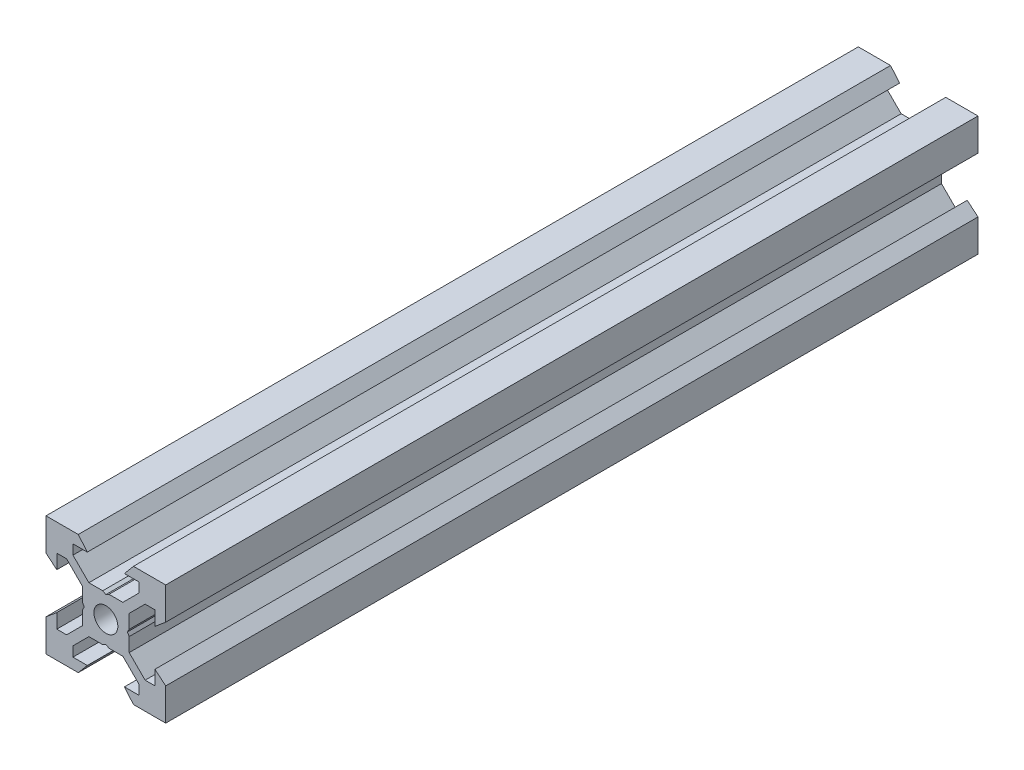
SolidWorks part; units mm, degrees
ref_plane "Front Plane" through (0, 0, 0) normal (0, 0, 1) x (1, 0, 0)
ref_plane "Top Plane" through (0, 0, 0) normal (0, 1, 0) x (1, 0, 0)
ref_plane "Right Plane" through (0, 0, 0) normal (1, 0, 0) x (0, 0, -1)
sketch "Sketch1" plane through (0, 0, 0) normal (0, 0, 1) x (1, 0, 0)
  line L0 (10, 10) -> (4.6104, 10) construction
  line L1 (10, 10) -> (10, 4.6104) construction
  line L2 (10, -10) -> (10, -4.6104) construction
  line L3 (10, -10) -> (4.6104, -10) construction
  line L4 (10, 10) -> (10, 4.6104)
  line L5 (6.5607, 5.5) -> (8.2, 5.5)
  line L6 (5.5, 8.2) -> (5.5, 6.5607)
  line L7 (10, 10) -> (4.6104, 10)
  line L8 (10, 10) -> (10, 4.6104)
  line L9 (6.5607, 5.5) -> (3.9, 2.8393)
  line L10 (5.5, 6.5607) -> (2.8393, 3.9)
  line L11 (10, 4.6104) -> (8.2, 3.1)
  line L12 (4.6104, 10) -> (3.1, 8.2)
  line L13 (8.2, 3.1) -> (8.2, 5.5)
  line L14 (3.1, 8.2) -> (5.5, 8.2)
  line L15 (-6.5607, 5.5) -> (-8.2, 5.5)
  line L16 (6.5607, -5.5) -> (8.2, -5.5)
  line L17 (3.1, -8.2) -> (5.5, -8.2)
  line L18 (8.2, -3.1) -> (8.2, -5.5)
  line L19 (4.6104, -10) -> (3.1, -8.2)
  line L20 (10, -4.6104) -> (8.2, -3.1)
  line L21 (0.5196, -3.9) -> (0, -3.6)
  line L22 (0.5196, 3.9) -> (0, 3.6)
  line L23 (3.6, 0) -> (3.9, -0.5196)
  line L24 (3.9, 0.5196) -> (3.6, 0)
  line L25 (3.9, 0.5196) -> (3.9, 2.8393)
  line L26 (2.8393, 3.9) -> (0.5196, 3.9)
  line L27 (3.9, -2.8393) -> (3.9, -0.5196)
  line L28 (2.8393, -3.9) -> (0.5196, -3.9)
  line L29 (5.5, -6.5607) -> (2.8393, -3.9)
  line L30 (6.5607, -5.5) -> (3.9, -2.8393)
  line L31 (10, -10) -> (10, -4.6104)
  line L32 (10, -10) -> (4.6104, -10)
  line L33 (5.5, -8.2) -> (5.5, -6.5607)
  line L34 (-6.5607, -5.5) -> (-8.2, -5.5)
  line L35 (10, -10) -> (10, -4.6104)
  line L36 (0, 0) -> (0, 8.2) construction
  line L37 (-10, -10) -> (-4.6104, -10) construction
  line L38 (-10, -10) -> (-10, -4.6104) construction
  line L39 (-10, 10) -> (-10, 4.6104) construction
  line L40 (-10, 10) -> (-4.6104, 10) construction
  line L41 (-10, -10) -> (-10, -4.6104)
  line L43 (-5.5, -8.2) -> (-5.5, -6.5607)
  line L44 (-10, -10) -> (-4.6104, -10)
  line L45 (-10, -10) -> (-10, -4.6104)
  line L46 (-6.5607, -5.5) -> (-3.9, -2.8393)
  line L47 (-5.5, -6.5607) -> (-2.8393, -3.9)
  line L48 (-2.8393, -3.9) -> (-0.5196, -3.9)
  line L49 (-3.9, -2.8393) -> (-3.9, -0.5196)
  line L50 (-2.8393, 3.9) -> (-0.5196, 3.9)
  line L51 (-3.9, 0.5196) -> (-3.9, 2.8393)
  line L52 (-3.9, 0.5196) -> (-3.6, 0)
  line L53 (-3.6, 0) -> (-3.9, -0.5196)
  line L54 (-0.5196, 3.9) -> (0, 3.6)
  line L55 (-0.5196, -3.9) -> (0, -3.6)
  line L56 (-10, -4.6104) -> (-8.2, -3.1)
  line L57 (-4.6104, -10) -> (-3.1, -8.2)
  line L58 (-8.2, -3.1) -> (-8.2, -5.5)
  line L59 (-3.1, -8.2) -> (-5.5, -8.2)
  line L60 (-10, -10) -> (10, -10) construction
  line L61 (-10, -10) -> (-10, 10) construction
  line L62 (-3.1, 8.2) -> (-5.5, 8.2)
  line L63 (-8.2, 3.1) -> (-8.2, 5.5)
  line L64 (-4.6104, 10) -> (-3.1, 8.2)
  line L65 (-10, 4.6104) -> (-8.2, 3.1)
  line L66 (-5.5, 6.5607) -> (-2.8393, 3.9)
  line L67 (-6.5607, 5.5) -> (-3.9, 2.8393)
  line L68 (-10, 10) -> (-10, 4.6104)
  line L69 (-10, 10) -> (-4.6104, 10)
  line L70 (-5.5, 8.2) -> (-5.5, 6.5607)
  line L71 (-10, 10) -> (10, 10) construction
  line L72 (-10, 10) -> (-10, 4.6104)
  line L73 (10, -10) -> (10, 10) construction
  line L74 (-10, -10) -> (10, 10) construction
  line L75 (-10, 10) -> (10, -10) construction
  circle A0 centre (0, 0) radius 2
  dimension "D7" = 4
  dimension "D1" = 20
  dimension "D2" = 5.3896
  dimension "D3" = 4.5
  dimension "D4" = 50
  dimension "D5" = 1.8
  dimension "D6" = 1.5104
  dimension "D8" = 5.5
  dimension "D9" = 120
  dimension "D10" = 0.3
  dimension "D11" = 2.3197
  dimension "D12" = 7.8
  dimension "D13" = 7.8
  dimension "D14" = 1.5
  dimension "D15" = 2.6607
extrude "Boss-Extrude1" add sketch "Sketch1" along normal mid plane 135.71 contours L70 L62 L64 L69 L68 L65 L63 L15 L67 L51 L52 L53 L49 L46 L34 L58 L56 L41 L44 L57 L59 L43 L47 L48 L55 L21 L28 L29 L33 L17 L19 L32 L31 L20 L18 L16 L30 L27 L23 L24 L25 L9 L5 L13 L11 L4 L7 L12 L14 L6 L10 region at (9.7172, 7.3052, 0)
